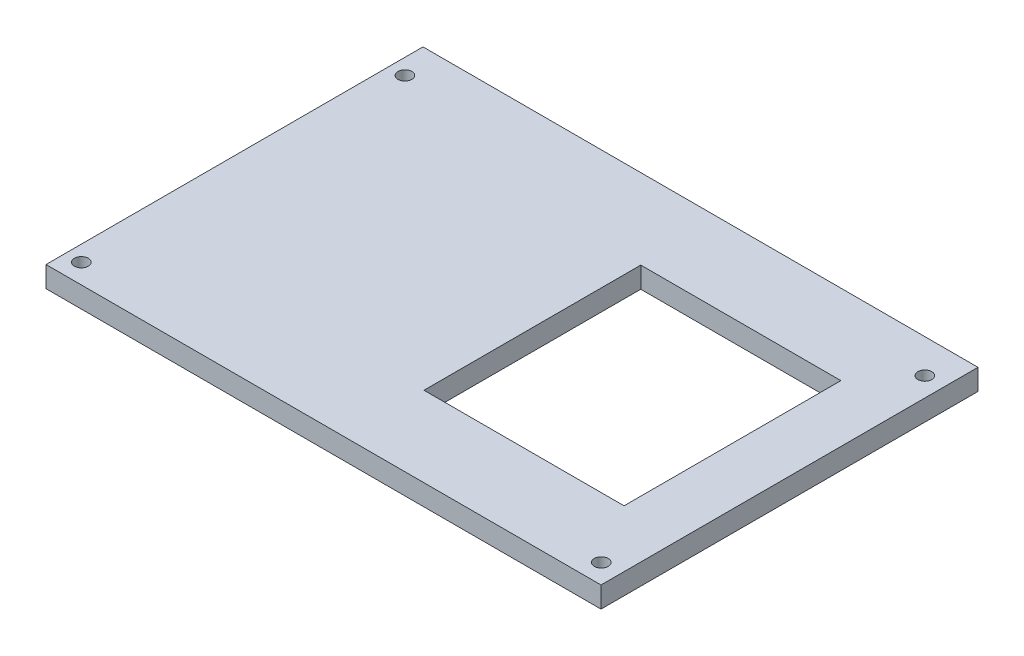
SolidWorks part; units mm, degrees
ref_plane "Front Plane" through (0, 0, 0) normal (0, 0, 1) x (1, 0, 0)
ref_plane "Top Plane" through (0, 0, 0) normal (0, 1, 0) x (1, 0, 0)
ref_plane "Right Plane" through (0, 0, 0) normal (1, 0, 0) x (0, 0, -1)
sketch "Sketch2" plane through (0, 0, 0) normal (0, 0, 1) x (1, 0, 0)
  line L1 (-53, 2) -> (53, 2)
  line L2 (-53, 2) -> (-53, -2)
  line L3 (-53, -2) -> (53, -2)
  line L4 (53, 2) -> (53, -2)
  line L5 (-53, 2) -> (53, -2) construction
  line L6 (-53, -2) -> (53, 2) construction
  point P0 (0, 0)
  dimension "D1" = 106
  dimension "D2" = 4
extrude "Boss-Extrude1" add sketch "Sketch2" along normal blind 72
sketch "Sketch4" plane through (0, 2, 0) normal (0, 1, 0) x (1, 0, 0)
  line L0 (-53, -72) -> (53, -72) construction
  line L1 (53, -72) -> (53, 0) construction
  line L2 (-62.6793, -72) -> (-62.6793, -4) construction
  line L3 (-50.0049, -4) -> (-53, -4) construction
  line L4 (-53, -72) -> (-53, 0) construction
  line L5 (-53, -4) -> (53, -4) construction
  line L6 (-56.8726, -4) -> (-56.8726, -6.4507) construction
  line L7 (-55.3882, -72) -> (-55.3882, -68.2507) construction
  line L8 (53, -77.5021) -> (49.2951, -77.5021) construction
  line L9 (53, 3.1613) -> (49.2951, 3.1613) construction
  line L10 (-53.7098, 3.1613) -> (-50.0049, 3.1613) construction
  line L11 (-53, -36) -> (53, -36) construction
  line L12 (0, 0) -> (0, -72) construction
  line L13 (53, 0) -> (-53, 0) construction
  circle A0 centre (-50.0049, -68.2507) radius 1.325
  circle A1 centre (49.2951, -68.2507) radius 1.325
  circle A2 centre (49.2951, -6.4507) radius 1.325
  circle A3 centre (-50.0049, -6.4507) radius 1.325
  dimension "D6" = 2.65
  dimension "D1" = 106
  dimension "D2" = 72
  dimension "D3" = 68
  dimension "D4" = 99.3
  dimension "D5" = 61.8
extrude "Cut-Extrude1" cut sketch "Sketch4" against normal through all contours A3 | A0 | A1 | A2 region at (-50.0049, 2, 68.2507) region at (49.2951, 2, 68.2507) region at (49.2951, 2, 6.4507) region at (-50.0049, 2, 6.4507)
sketch "Sketch5" plane through (0, 0, 0) normal (0, 0, -1) x (-1, 0, 0)
  line L0 (-53, 0) -> (53, 0) construction
  line L1 (-53, -2) -> (-53, 2) construction
  line L2 (53, 2) -> (53, -2) construction
  circle A0 centre (0, 0) radius 1.75
  circle A1 centre (26.5, 0) radius 1.75
  circle A2 centre (-26.5, 0) radius 1.75
  dimension "D3" = 3.5
  dimension "D1" = 26.5
  dimension "D2" = 26.5
extrude "Cut-Extrude2" cut sketch "Sketch5" against normal blind 10
sketch "Sketch6" plane through (0, 2, 0) normal (0, 1, 0) x (1, 0, 0)
  line L0 (0, 0) -> (0, -72) construction
  line L1 (53, -72) -> (-53, -72) construction
  line L2 (-53, -36) -> (53, -36) construction
  line L3 (-53, -72) -> (-53, 0) construction
  line L4 (53, -72) -> (53, 0) construction
  line L6 (3.8895, -15.2958) -> (42.1105, -15.2958)
  line L7 (3.8895, -15.2958) -> (3.8895, -56.7042)
  line L8 (3.8895, -56.7042) -> (42.1105, -56.7042)
  line L9 (42.1105, -15.2958) -> (42.1105, -56.7042)
  line L10 (3.8895, -15.2958) -> (42.1105, -56.7042) construction
  line L11 (3.8895, -56.7042) -> (42.1105, -15.2958) construction
  point P11 (23, -36)
  dimension "D1" = 23
  dimension "D2" = 30
extrude "Cut-Extrude3" cut sketch "Sketch6" against normal blind 10
